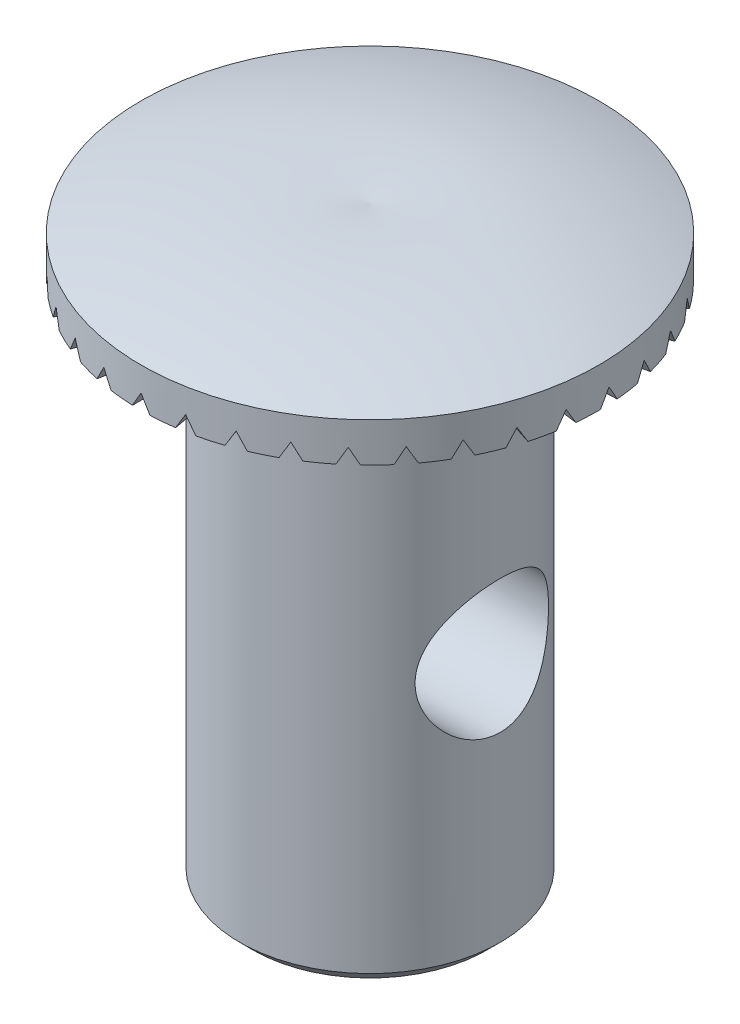
SolidWorks part; units mm, degrees
material "Alumina"
ref_plane "Plano frontal" through (0, 0, 0) normal (0, 0, 1) x (1, 0, 0)
ref_plane "Plano superior" through (0, 0, 0) normal (0, 1, 0) x (1, 0, 0)
ref_plane "Plano direito" through (0, 0, 0) normal (1, 0, 0) x (0, 0, -1)
sketch "Esboço1" plane through (0, 0, 0) normal (0, 0, 1) x (1, 0, 0)
  line L0 (9.95, 0) -> (17.5, 0)
  line L1 (17.5, 0) -> (17.5, 3)
  line L2 (0, 5) -> (0, 0)
  line L3 (9.95, 0) -> (9.95, -40)
  line L4 (9.95, -40) -> (0, -40)
  line L5 (0, -40) -> (0, 0)
  arc A2 (17.5, 3) -> (0, 5) centre (4.3196, -34.7661) ccw
  dimension "D1" = 17.5
  dimension "D2" = 3
  dimension "D4" = 40
  dimension "D3" = 5
  dimension "D5" = 9.95
  dimension "D6" = 40
  dimension "D7" = 5
revolve "Revolução1" add sketch "Esboço1" angle 360 about L5
ref_plane "Plano1" through (0, 0, 19) normal (0, 0, 1) x (1, 0, 0)
sketch "Esboço2" plane through (0, 0, 19) normal (0, 0, 1) x (1, 0, 0)
  line L1 (0, 1.1547) -> (-1, -0.5774)
  line L2 (-1, -0.5774) -> (1, -0.5774)
  line L3 (1, -0.5774) -> (0, 1.1547)
  circle A0 centre (0, 0) radius 0.5774 construction
  dimension "D1" = 1.1547
extrude "Corte-extrusão1" cut sketch "Esboço2" against normal up to surface (9.1004 mm away) up to face at (0, 0, -9.95)
pattern_circular "PadrãoCircular1" count 35 over 360 about axis through (0, 0, 0) along (0, -1, 0) of "Corte-extrusão1"
hole_wizard "Furo roscado de M81" positions "Esboço3" profile "Esboço5" tap size "M8" standard "DIN"
sketch "Esboço3" plane through (0, -40, 0) normal (0, -1, 0) x (-1, 0, 0)
  point P0 (0, 0)
sketch "Esboço5" plane through (0, -40, 0) normal (1, 0, 0) x (0, 0, -1)
  line L0 (0, 0) -> (0, 16.0429)
  line L1 (0, 16.0429) -> (3.4, 14)
  line L2 (3.4, 14) -> (3.4, 0.625)
  line L3 (3.4, 0.625) -> (4.025, 0)
  line L5 (4.025, 0) -> (0, 0)
  line L6 (-3.4, 0.625) -> (-4.025, 0) construction
  line L10 (0, 16.0429) -> (-3.4, 14) construction
  line L11 (0, -6.35) -> (0, 107.95) construction
  dimension "Tap Drill Dia." = 6.8
  dimension "Tap Drill Depth" = 14
  dimension "Near C'Sink Dia." = 8.05
  dimension "Near C'Sink Angle" = 90
  dimension "Drill Angle" = 118
cosmetic thread "Rosca de furo1" parameters "D1"=12, "D2"=8
ref_plane "Plano2" through (19, 0, 0) normal (-1, 0, 0) x (0, 0, 1)
hole_wizard "Furo roscado de M121" positions "Esboço8" profile "Esboço9" tap size "M12" standard "DIN"
sketch "Esboço8" plane through (19, 0, 0) normal (-1, 0, 0) x (0, 0, 1)
  line L0 (-9.95, -40) -> (9.95, -40) construction
  line L1 (0, 0) -> (0, -20) construction
  point P0 (0, -20)
  dimension "D1" = 20
sketch "Esboço9" plane through (19, -20, 0) normal (0, 1, 0) x (0, 0, -1)
  line L0 (0, 0) -> (0, 75.8144)
  line L1 (0, 75.8144) -> (5.1, 72.75)
  line L2 (5.1, 72.75) -> (5.1, 0.925)
  line L3 (5.1, 0.925) -> (6.025, 0)
  line L5 (6.025, 0) -> (0, 0)
  line L6 (-5.1, 0.925) -> (-6.025, 0) construction
  line L10 (0, 75.8144) -> (-5.1, 72.75) construction
  line L11 (0, -6.35) -> (0, 107.95) construction
  dimension "Tap Drill Dia." = 10.2
  dimension "Tap Drill Depth" = 72.75
  dimension "Near C'Sink Dia." = 12.05
  dimension "Near C'Sink Angle" = 90
  dimension "Drill Angle" = 118
cosmetic thread "Rosca de furo2" parameters "D1"=24, "D2"=12
chamfer "Chanfro1" distance 1 angle 45 1 edges at (0, -40, -9.95)
